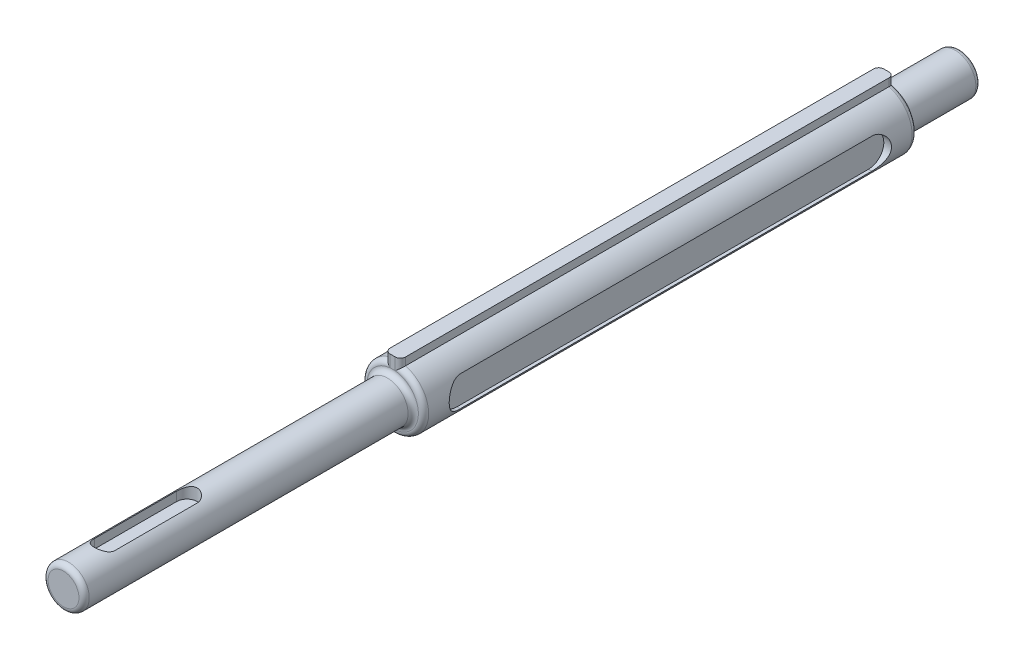
SolidWorks part; units mm, degrees
material "AISI 1020"
ref_plane "Front Plane" through (0, 0, 0) normal (0, 0, 1) x (1, 0, 0)
ref_plane "Top Plane" through (0, 0, 0) normal (0, 1, 0) x (1, 0, 0)
ref_plane "Right Plane" through (0, 0, 0) normal (1, 0, 0) x (0, 0, -1)
sketch "Sketch1" plane through (0, 0, 0) normal (0, 0, 1) x (1, 0, 0)
  line L0 (1.1906, 4.6113) -> (1.1906, 5.8019)
  line L1 (1.1906, 5.8019) -> (-1.1906, 5.8019)
  line L2 (-1.1906, 5.8019) -> (-1.1906, 4.6113)
  arc A0 (-1.1906, 4.6113) -> (1.1906, 4.6113) centre (0, 0) ccw
  point P4 (0, 5.8019)
  dimension "D1" = 4.7625
  dimension "D2" = 1.1906
  dimension "D3" = 2.3813
extrude "Boss-Extrude1" add sketch "Sketch1" along normal blind 76.2
sketch "Sketch2" plane through (0, 0, 0) normal (0, 0, -1) x (-1, 0, 0)
  circle A0 centre (0, 0) radius 3.175
  dimension "D1" = 6.35
extrude "Boss-Extrude2" add sketch "Sketch2" along normal blind 11.43
sketch "Sketch3" plane through (0, 0, 76.2) normal (0, 0, 1) x (1, 0, 0)
  circle A0 centre (0, 0) radius 3.175
  dimension "D1" = 6.35
extrude "Boss-Extrude3" add sketch "Sketch3" along normal blind 50.8
fillet "Fillet1" radius 0.7937 10 edges at (0, -4.7625, 0) (-3.175, 0, 0) (3.175, 0, 76.2) (0, -4.7625, 76.2) (1.1906, 5.2066, 0) (-1.1906, 5.2066, 0) (1.1906, 5.2066, 76.2) (-1.1906, 5.2066, 76.2) (-3.175, 0, -11.43) (3.175, 0, 127)
ref_plane "Plane1" through (0, 0, 0) normal (1, 0, 0) x (0, 0, -1)
ref_plane "Plane2" through (4.7625, 0, 0) normal (1, 0, 0) x (0, 0, -1)
sketch "Sketch4" plane through (4.7625, 0, 0) normal (1, 0, 0) x (0, 0, -1)
  line L0 (-75.4063, -0.0756) -> (-0.7938, -0.0756) construction
  line L1 (-75.4063, 4.6113) -> (-75.4063, -4.7625) construction
  line L2 (-0.7937, -4.7625) -> (-0.7938, 4.6113) construction
  line L3 (-69.85, -0.0756) -> (-6.35, -0.0756) construction
  line L4 (-69.85, 2.3056) -> (-6.35, 2.3056)
  line L5 (-69.85, -2.4569) -> (-6.35, -2.4569)
  arc A0 (-69.85, 2.3056) -> (-69.85, -2.4569) centre (-69.85, -0.0756) ccw
  arc A1 (-6.35, -2.4569) -> (-6.35, 2.3056) centre (-6.35, -0.0756) ccw
  point P8 (-38.1, -0.0756)
  point P13 (-38.1, -0.0756)
  dimension "D1" = 2.3813
  dimension "D2" = 31.75
extrude "Cut-Extrude1" cut sketch "Sketch4" against normal blind 1.1906
ref_plane "Plane3" through (0, 5.8019, 0) normal (0, 1, 0) x (1, 0, 0)
sketch "Sketch5" plane through (0, 5.8019, 0) normal (0, 1, 0) x (1, 0, 0)
  line L0 (0, -76.9938) -> (0, -127) construction
  line L1 (3.175, -76.9938) -> (-3.175, -76.9938) construction
  line L2 (-3.175, -127) -> (3.175, -127) construction
  line L3 (0, -120.65) -> (0, -107.95) construction
  line L4 (-1.5875, -120.65) -> (-1.5875, -107.95)
  line L5 (1.5875, -120.65) -> (1.5875, -107.95)
  arc A0 (-1.5875, -120.65) -> (1.5875, -120.65) centre (0, -120.65) ccw
  arc A1 (1.5875, -107.95) -> (-1.5875, -107.95) centre (0, -107.95) ccw
  point P8 (0, -114.3)
  dimension "D1" = 1.5875
  dimension "D2" = 12.7
  dimension "D3" = 6.35
extrude "Cut-Extrude2" cut sketch "Sketch5" against normal blind 4.445
mirror "Mirror1" about plane through (0, 0, 0) normal (1, 0, 0) of "Cut-Extrude1"
